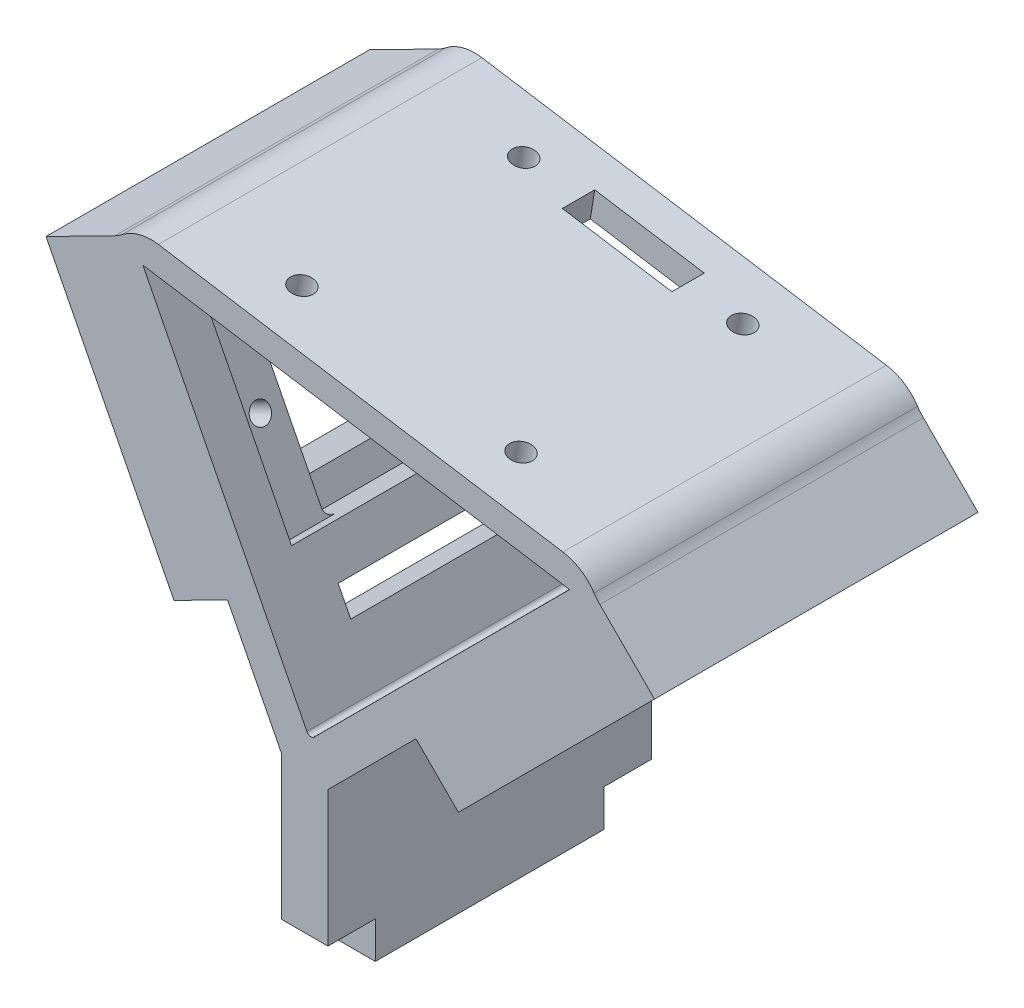
SolidWorks part; units mm, degrees
ref_plane "Front Plane" through (0, 0, 0) normal (0, 0, 1) x (1, 0, 0)
ref_plane "Top Plane" through (0, 0, 0) normal (0, 1, 0) x (1, 0, 0)
ref_plane "Right Plane" through (0, 0, 0) normal (1, 0, 0) x (0, 0, -1)
sketch "Sketch1" plane through (0, 0, 0) normal (0, 0, 1) x (1, 0, 0)
  line L0 (6.55, 4.55) -> (-6.55, 4.55)
  line L1 (4.05, 2.05) -> (-4.05, 2.05)
  line L2 (4.05, 2.05) -> (4.05, -2.05)
  line L3 (4.05, -2.05) -> (2.05, -2.05)
  line L4 (-4.05, 2.05) -> (-4.05, -2.05)
  line L5 (4.05, 2.05) -> (-4.05, -2.05) construction
  line L6 (4.05, -2.05) -> (-4.05, 2.05) construction
  line L7 (-6.55, 4.55) -> (-6.55, -4.55)
  line L8 (6.55, -4.55) -> (2.05, -4.55)
  line L9 (6.55, 4.55) -> (6.55, -4.55)
  line L10 (0, 0) -> (0, -4.55) construction
  line L11 (-2.05, -2.05) -> (-2.05, -4.55)
  line L12 (2.05, -2.05) -> (2.05, -4.55)
  line L13 (-2.05, -4.55) -> (-6.55, -4.55)
  line L14 (6.55, -4.55) -> (-6.55, -4.55) construction
  line L15 (-2.05, -2.05) -> (-4.05, -2.05)
  line L16 (4.05, -2.05) -> (-4.05, -2.05) construction
  line L17 (0, -2.05) -> (0, -4.55) construction
  point P0 (0, 0)
  dimension "D1" = 8.1
  dimension "D2" = 4.1
  dimension "D6" = 4.1
  dimension "D3" = 2.5
  dimension "D4" = 2.05
  dimension "D5" = 2.05
extrude "Boss-Extrude1" add sketch "Sketch1" along normal blind 35
sketch "Sketch2" plane through (0, 0, 35) normal (0, 0, 1) x (1, 0, 0)
  line L0 (0, 4.55) -> (0, 29.55) construction
  line L1 (6.55, 4.55) -> (-6.55, 4.55) construction
  line L2 (2.5, 4.55) -> (2.5, 25.7216)
  line L3 (-2.5, 4.55) -> (-2.5, 26.5511)
  line L4 (-2.5, 4.55) -> (2.5, 4.55)
  line L6 (0, 26.05) -> (31.8198, 57.8698) construction
  line L7 (0, 26.05) -> (-20.4296, 66.1453) construction
  line L8 (2.5, 25.7216) -> (33.234, 56.4556)
  line L9 (0.5323, 29.4107) -> (30.4056, 59.284)
  line L10 (1.4142, 24.6358) -> (33.234, 56.4556) construction
  line L11 (-2.5, 26.5511) -> (-22.2116, 65.2373)
  line L12 (-1.782, 25.142) -> (-22.2116, 65.2373) construction
  line L13 (-1.4142, 27.4642) -> (30.4056, 59.284) construction
  line L14 (0.5323, 29.4107) -> (-18.6476, 67.0533)
  line L15 (2.5, 4.55) -> (2.5, 29.55) construction
  line L17 (-2.5, 4.55) -> (-2.5, 29.55) construction
  line L18 (30.4056, 59.284) -> (33.234, 56.4556)
  line L19 (-22.2116, 65.2373) -> (-18.6476, 67.0533)
  dimension "D1" = 25
  dimension "D4" = 27
  dimension "D5" = 45
  dimension "D6" = 3.5
  dimension "D7" = 45
  dimension "D8" = 45
  dimension "D11" = 2
  dimension "D2" = 2.5
  dimension "D3" = 2.5
  dimension "D9" = 2
  dimension "D10" = 2
  dimension "D12" = 2
extrude "Boss-Extrude2" add sketch "Sketch2" against normal through all
fillet "Fillet1" radius 0.5 1 edges at (0.5323, 29.4107, 17.5)
sketch "Sketch3" plane through (-14.4392, 14.4392, 0) normal (-0.7071, 0.7071, 0) x (0, 0, 1)
  line L0 (0, 63.4201) -> (35, 63.4201) construction
  line L1 (4.5, 60.4201) -> (30.5, 60.4201)
  line L2 (4.5, 60.4201) -> (4.5, 35.4201)
  line L3 (4.5, 35.4201) -> (30.5, 35.4201)
  line L4 (30.5, 60.4201) -> (30.5, 35.4201)
  line L5 (4.5, 60.4201) -> (30.5, 35.4201) construction
  line L6 (4.5, 35.4201) -> (30.5, 60.4201) construction
  line L7 (17.5, 47.9201) -> (17.5, 63.4201) construction
  point P0 (17.5, 47.9201)
  dimension "D1" = 3
  dimension "D2" = 25
  dimension "D3" = 26
extrude "Cut-Extrude1" cut sketch "Sketch3" against normal blind 1.5
sketch "Sketch4" plane through (-13.3786, 13.3786, 0) normal (-0.7071, 0.7071, 0) x (0, 0, 1)
  line L2 (25.5, 35.4201) -> (25.5, 60.4201)
  line L3 (25.5, 35.4201) -> (25.5, 60.4201)
  line L4 (9.5, 60.4201) -> (25.5, 60.4201)
  line L5 (9.5, 60.4201) -> (9.5, 35.4201)
  line L6 (9.5, 60.4201) -> (9.5, 35.4201)
  line L7 (9.5, 35.4201) -> (26.4646, 35.4201)
  line M4 (30.5, 60.4201) -> (4.5, 60.4201)
  line M6 (4.5, 35.4201) -> (30.5, 35.4201)
  dimension "D1" = 5
  dimension "D2" = 5
extrude "Cut-Extrude2" cut sketch "Sketch4" against normal blind 5 contours L6 L3 M4 M6 region at (20.5061, 47.2632, 17.5)
fillet "Fillet3" radius 1 4 edges at (30.2288, 55.2182, 9.5) (30.2288, 55.2182, 25.5) (12.5511, 37.5405, 25.5) (12.5511, 37.5405, 9.5)
sketch "Sketch5" plane through (12.3195, 6.2771, 0) normal (0.891, 0.454, 0) x (0, 0, -1)
  line L0 (-17.5, 68.2107) -> (-17.5, 52.7107) construction
  line L1 (-30.5, 65.2107) -> (-4.5, 65.2107)
  line L2 (-30.5, 65.2107) -> (-30.5, 40.2107)
  line L3 (-30.5, 40.2107) -> (-4.5, 40.2107)
  line L4 (-4.5, 65.2107) -> (-4.5, 40.2107)
  line L5 (-30.5, 65.2107) -> (-4.5, 40.2107) construction
  line L6 (-30.5, 40.2107) -> (-4.5, 65.2107) construction
  line L7 (0, 68.2107) -> (-35, 68.2107) construction
  point P0 (-17.5, 52.7107)
  dimension "D1" = 3
  dimension "D2" = 25
  dimension "D3" = 26
extrude "Cut-Extrude3" cut sketch "Sketch5" against normal blind 1.5
sketch "Sketch6" plane through (10.9829, 5.5961, 0) normal (0.891, 0.454, 0) x (0, 0, -1)
  line L2 (-25.5, 65.2107) -> (-25.5, 40.2107)
  line L3 (-25.5, 65.2107) -> (-25.5, 40.2107)
  line L4 (-9.5, 65.2107) -> (-25.5, 65.2107)
  line L5 (-9.5, 40.2107) -> (-9.5, 65.2107)
  line L6 (-9.5, 40.2107) -> (-9.5, 65.2107)
  line L7 (-25.5, 40.2107) -> (-9.5, 40.2107)
  dimension "D1" = 5
  dimension "D2" = 5
extrude "Cut-Extrude4" cut sketch "Sketch6" against normal blind 5
fillet "Fillet4" radius 1 4 edges at (-8.3861, 40.8566, 9.5) (-19.7359, 63.1318, 9.5) (-19.7359, 63.1318, 25.5) (-8.3861, 40.8566, 25.5)
sketch "Sketch8" plane through (-11.6108, 11.6108, 0) normal (0.7071, -0.7071, 0) x (0, 0, -1)
  line L0 (-17.5, 29.4201) -> (-17.5, 35.4201) construction
  line L1 (-27.5, 30.9201) -> (-7.5, 30.9201)
  line L2 (-27.5, 30.9201) -> (-27.5, 27.9201)
  line L3 (-27.5, 27.9201) -> (-7.5, 27.9201)
  line L4 (-7.5, 30.9201) -> (-7.5, 27.9201)
  line L5 (-27.5, 30.9201) -> (-7.5, 27.9201) construction
  line L6 (-27.5, 27.9201) -> (-7.5, 30.9201) construction
  line L7 (-24.5, 35.4201) -> (-10.5, 35.4201) construction
  point P0 (-17.5, 29.4201)
  dimension "D1" = 3
  dimension "D2" = 6
  dimension "D3" = 20
extrude "Cut-Extrude5" cut sketch "Sketch8" against normal blind 4
sketch "Sketch9" plane through (8.7554, 4.4611, 0) normal (-0.891, -0.454, 0) x (0, 0, 1)
  line L0 (17.5, 40.2107) -> (17.5, 34.2107) construction
  line L2 (10.5, 40.2107) -> (24.5, 40.2107) construction
  line L3 (7.5, 35.7107) -> (27.5, 35.7107)
  line L4 (7.5, 35.7107) -> (7.5, 32.7107)
  line L5 (7.5, 32.7107) -> (27.5, 32.7107)
  line L6 (27.5, 35.7107) -> (27.5, 32.7107)
  line L7 (7.5, 35.7107) -> (27.5, 32.7107) construction
  line L8 (7.5, 32.7107) -> (27.5, 35.7107) construction
  dimension "D1" = 6
  dimension "D2" = 20
  dimension "D3" = 3
extrude "Cut-Extrude6" cut sketch "Sketch9" against normal blind 4
sketch "Sketch10" plane through (-2.5, 0, 0) normal (-1, 0, 0) x (0, 0, 1)
  line L2 (17.5, 4.55) -> (17.5, 19.55) construction
  line L3 (35, 4.55) -> (0, 4.55) construction
  line L4 (7.5, 21.05) -> (27.5, 21.05)
  line L5 (7.5, 21.05) -> (7.5, 18.05)
  line L6 (7.5, 18.05) -> (27.5, 18.05)
  line L7 (27.5, 21.05) -> (27.5, 18.05)
  line L8 (7.5, 21.05) -> (27.5, 18.05) construction
  line L9 (7.5, 18.05) -> (27.5, 21.05) construction
  point P6 (17.5, 19.55)
  dimension "D1" = 20
  dimension "D2" = 3
  dimension "D3" = 15
extrude "Cut-Extrude7" cut sketch "Sketch10" against normal blind 4
sketch "Sketch11" plane through (-13.3786, 13.3786, 0) normal (-0.7071, 0.7071, 0) x (0, 0, 1)
  line L0 (7, 45.4201) -> (7, 57.9201) construction
  line L1 (7, 57.9201) -> (28, 57.9201) construction
  line L2 (28, 57.9201) -> (28, 45.4201) construction
  line L3 (28, 45.4201) -> (7, 45.4201) construction
  line L4 (30.5, 60.4201) -> (4.5, 60.4201) construction
  line L5 (4.5, 60.4201) -> (4.5, 35.4201) construction
  circle A1 centre (28, 57.9201) radius 1.1
  circle A3 centre (7, 57.9201) radius 1.1
  circle A5 centre (28, 45.4201) radius 1.1
  circle A7 centre (7, 45.4201) radius 1.1
  dimension "D3" = 2.2
  dimension "D1" = 21
  dimension "D2" = 12.5
  dimension "D4" = 2.5
  dimension "D5" = 2.5
extrude "Cut-Extrude8" cut sketch "Sketch11" against normal blind 10
sketch "Sketch12" plane through (10.9829, 5.5961, 0) normal (0.891, 0.454, 0) x (0, 0, -1)
  line L0 (-28, 62.7107) -> (-28, 50.2107) construction
  line L2 (-28, 50.2107) -> (-7, 50.2107) construction
  line L5 (-7, 50.2107) -> (-7, 62.7107) construction
  line L6 (-7, 62.7107) -> (-28, 62.7107) construction
  line L7 (-4.5, 65.2107) -> (-30.5, 65.2107) construction
  line L8 (-30.5, 65.2107) -> (-30.5, 40.2107) construction
  circle A1 centre (-7, 62.7107) radius 1.1
  circle A3 centre (-28, 62.7107) radius 1.1
  circle A5 centre (-7, 50.2107) radius 1.1
  circle A7 centre (-28, 50.2107) radius 1.1
  dimension "D5" = 2.2
  dimension "D1" = 12.5
  dimension "D2" = 21
  dimension "D3" = 2.5
  dimension "D4" = 2.5
extrude "Cut-Extrude9" cut sketch "Sketch12" against normal blind 5
sketch "Sketch14" plane through (6.55, 0, 0) normal (1, 0, 0) x (0, 0, -1)
  line L0 (-35, -0.1) -> (0, 0) construction
  line L3 (-35, 1.8508) -> (0, 1.8508)
  line L4 (-35, 1.8508) -> (-35, -1.9508)
  line L5 (-35, -1.9508) -> (0, -1.9508)
  line L6 (0, 1.8508) -> (0, -1.9508)
  line L7 (-35, 1.8508) -> (0, -1.9508) construction
  line L8 (-35, -1.9508) -> (0, 1.8508) construction
  point P5 (-17.5, -0.05)
extrude "Boss-Extrude3" add sketch "Sketch14" along normal blind 3.5 and the other way blind 1
sketch "Sketch15" plane through (0, 1.8508, 0) normal (0, 1, 0) x (1, 0, 0)
  line L6 (6.55, -35) -> (6.55, 0) construction
  line L7 (6.55, -33) -> (6.55, -2)
  line L9 (8.05, -33) -> (6.55, -33)
  line L10 (6.55, -2) -> (8.05, -2)
  line L11 (8.05, -2) -> (8.05, -33)
  line L12 (8.05, -33) -> (6.55, -33)
  line L13 (6.55, -2) -> (8.05, -2)
  line L14 (8.05, -2) -> (8.05, -33)
  dimension "D1" = 2
extrude "Cut-Extrude10" cut sketch "Sketch15" against normal blind 5
sketch "Sketch16" plane through (0, 4.55, 0) normal (0, 1, 0) x (1, 0, 0)
  line L1 (-30.4197, 7.2021) -> (26.8386, 7.2021)
  line L2 (-30.4197, 7.2021) -> (-30.4197, -38.2329)
  line L3 (-30.4197, -38.2329) -> (26.8386, -38.2329)
  line L4 (26.8386, 7.2021) -> (26.8386, -38.2329)
  line L5 (-30.4197, 7.2021) -> (26.8386, -38.2329) construction
  line L6 (-30.4197, -38.2329) -> (26.8386, 7.2021) construction
  point P0 (-1.7905, -15.5154)
extrude "Cut-Extrude11" [suppressed] cut sketch "Sketch16" against normal blind 10 and the other way blind 1
sketch "Sketch18" plane through (-11.6108, 11.6108, 0) normal (0.7071, -0.7071, 0) x (0, 0, -1)
  line L0 (-35, 19.9557) -> (-35, 63.4201) construction
  line L1 (0, 19.9557) -> (0, 63.4201) construction
  line L2 (0, 63.4201) -> (-35, 63.4201) construction
  line L3 (-35, 33.4201) -> (-35, 63.4201)
  line L4 (0, 33.4201) -> (0, 63.4201)
  line L5 (0, 63.4201) -> (-35, 63.4201)
  line L6 (-25.5, 59.4201) -> (-25.5, 36.4201) construction
  line L7 (-9.5, 36.4201) -> (-9.5, 59.4201) construction
  line L9 (-25.5, 58.9201) -> (-25.5, 38.9201)
  line L10 (-9.5, 38.9201) -> (-9.5, 58.9201)
  line L11 (-35, 33.4201) -> (0, 33.4201)
  line L12 (-25.5, 58.9201) -> (-9.5, 58.9201)
  line L13 (-25.5, 38.9201) -> (-9.5, 38.9201)
  line L14 (-24.5, 35.4201) -> (-10.5, 35.4201) construction
  circle A4 centre (-7, 57.9201) radius 1.1 construction
  circle A5 centre (-7, 45.4201) radius 1.1 construction
  circle A6 centre (-28, 45.4201) radius 1.1 construction
  circle A7 centre (-28, 57.9201) radius 1.1 construction
  circle A8 centre (-7, 57.9201) radius 1.1
  circle A9 centre (-7, 45.4201) radius 1.1
  circle A10 centre (-28, 45.4201) radius 1.1
  circle A11 centre (-28, 57.9201) radius 1.1
  dimension "D1" = 2
  dimension "D2" = 4.5
  dimension "D3" = 3.5
extrude "Boss-Extrude4" add sketch "Sketch18" along normal blind 6.5
sketch "Sketch19" plane through (8.7554, 4.4611, 0) normal (-0.891, -0.454, 0) x (0, 0, 1)
  line L0 (25.5, 41.2107) -> (25.5, 64.2107) construction
  line L1 (9.5, 64.2107) -> (9.5, 41.2107) construction
  line L2 (25.5, 43.2107) -> (25.5, 60.7107)
  line L3 (9.5, 60.7107) -> (9.5, 43.2107)
  line L4 (35, 68.2107) -> (0, 68.2107)
  line L5 (0, 68.2107) -> (0, 24.7922)
  line L6 (0, 24.7922) -> (35, 24.7922)
  line L7 (35, 24.7922) -> (35, 68.2107)
  line L8 (35, 68.2107) -> (0, 68.2107)
  line L9 (0, 68.2107) -> (0, 37.7107)
  line L11 (35, 37.7107) -> (35, 68.2107)
  line L12 (9.5, 60.7107) -> (25.5, 60.7107)
  line L13 (9.5, 43.2107) -> (25.5, 43.2107)
  line L14 (24.5, 65.2107) -> (10.5, 65.2107) construction
  line L15 (10.5, 40.2107) -> (24.5, 40.2107) construction
  line L16 (0, 37.7107) -> (35, 37.7107)
  circle A0 centre (28, 62.7107) radius 1.1 construction
  circle A1 centre (28, 50.2107) radius 1.1 construction
  circle A6 centre (7, 50.2107) radius 1.1 construction
  circle A7 centre (7, 62.7107) radius 1.1 construction
  circle A8 centre (28, 50.2107) radius 1.1
  circle A9 centre (7, 50.2107) radius 1.1
  circle A10 centre (7, 62.7107) radius 1.1
  circle A11 centre (28, 62.7107) radius 1.1
  dimension "D2" = 4.5
  dimension "D3" = 3
  dimension "D4" = 2.5
  dimension "D1" = 0
extrude "Boss-Extrude5" add sketch "Sketch19" along normal blind 6.5
sketch "Sketch20" plane through (0, 4.55, 0) normal (0, 1, 0) x (1, 0, 0)
  line L1 (-46.7008, 10.2311) -> (46.7008, 10.2311)
  line L2 (-46.7008, 10.2311) -> (-46.7008, -43.0242)
  line L3 (-46.7008, -43.0242) -> (46.7008, -43.0242)
  line L4 (46.7008, 10.2311) -> (46.7008, -43.0242)
  line L5 (-46.7008, 10.2311) -> (46.7008, -43.0242) construction
  line L6 (-46.7008, -43.0242) -> (46.7008, 10.2311) construction
  point P0 (0, -16.3965)
extrude "Cut-Extrude12" cut sketch "Sketch20" against normal blind 10 and the other way blind 2.5
sketch "Sketch21" plane through (0, 0, 35) normal (0, 0, 1) x (1, 0, 0)
  line L0 (2.5, 7.05) -> (2.5, 25.7216) construction
  line L1 (-2.5, 7.05) -> (2.5, 7.05)
  line L2 (-2.5, 7.05) -> (-2.5, 11.05)
  line L3 (-2.5, 11.05) -> (2.5, 11.05)
  line L4 (2.5, 7.05) -> (2.5, 11.05)
  dimension "D1" = 4
extrude "Cut-Extrude13" cut sketch "Sketch21" against normal blind 5.125
ref_plane "Plane1" through (0, 0, 17.5) normal (0, 0, -1) x (-1, 0, 0)
mirror "Mirror1" about plane through (0, 0, 17.5) normal (0, 0, -1) of "Cut-Extrude13"
fillet "Fillet9" radius 2 4 edges at (-21.7024, 57.0793, 25.5) (-13.7576, 41.4867, 9.5) (-13.7576, 41.4867, 25.5) (-21.7024, 57.0793, 9.5)
fillet "Fillet10" radius 2 4 edges at (32.3501, 50.9755, 9.5) (32.3501, 50.9755, 25.5) (18.208, 36.8334, 25.5) (18.208, 36.8334, 9.5)
sketch "Sketch22" plane through (0, 0, 35) normal (0, 0, 1) x (1, 0, 0)
  line L0 (-18.0758, 64.935) -> (29.4542, 57.407)
  line L1 (29.4542, 57.407) -> (32.8149, 56.8747)
  line L3 (32.8149, 56.8747) -> (30.4056, 59.284)
  line L4 (30.4056, 59.284) -> (-18.6476, 67.0533)
  line L5 (-18.6476, 67.0533) -> (-20.4498, 65.9701)
  line L7 (-20.4498, 65.9701) -> (-18.0758, 64.935)
  line L8 (37.8302, 51.8594) -> (30.4056, 59.284) construction
  point P4 (0, 0)
  point P6 (0, 0)
  point P13 (0, 0)
  point P14 (0, 0)
  point P15 (0, 0)
  point P16 (0, 0)
  point P17 (0, 0)
  point P20 (0, 0)
extrude "Boss-Extrude6" add sketch "Sketch22" against normal through all
sketch "Sketch23" plane through (9.904, 62.5312, 0) normal (0.1564, 0.9877, 0) x (0.9877, -0.1564, 0)
  line L4 (-28.9074, -35) -> (20.7572, -35)
  line L5 (-28.9074, 0) -> (-28.9074, -35)
  line L6 (20.7572, 0) -> (-28.9074, 0)
  line L8 (-28.9074, -35) -> (20.7572, -35)
  line L10 (20.7572, 0) -> (-28.9074, 0)
  line L12 (-28.9074, 0) -> (-28.9074, -35)
  line L14 (20.7572, -35) -> (20.7572, 0)
  line L16 (20.7572, -35) -> (20.7572, 0)
  dimension "D1" = 0
extrude "Boss-Extrude7" add sketch "Sketch23" along normal blind 1
sketch "Sketch24" plane through (10.0604, 63.5188, 0) normal (0.1564, 0.9877, 0) x (0.9877, -0.1564, 0)
  line L0 (-4.0751, -35) -> (-4.0751, 0) construction
  line L1 (-28.9074, -35) -> (20.7572, -35) construction
  line L2 (20.7572, 0) -> (-28.9074, 0) construction
  line L3 (-16.0751, -5.5) -> (-16.0751, -29.5) construction
  line L4 (-18.0751, -3.5) -> (9.9249, -3.5) construction
  line L5 (-18.0751, -3.5) -> (-18.0751, -31.5) construction
  line L6 (-18.0751, -31.5) -> (9.9249, -31.5) construction
  line L7 (9.9249, -3.5) -> (9.9249, -31.5) construction
  line L8 (-18.0751, -3.5) -> (9.9249, -31.5) construction
  line L9 (-18.0751, -31.5) -> (9.9249, -3.5) construction
  line L10 (-16.0751, -29.5) -> (7.9249, -29.5) construction
  line L11 (7.9249, -29.5) -> (7.9249, -5.5) construction
  line L12 (7.9249, -5.5) -> (-16.0751, -5.5) construction
  line L14 (-10.0751, -3.75) -> (1.9249, -3.75)
  line L15 (-10.0751, -3.75) -> (-10.0751, -7.25)
  line L16 (-10.0751, -7.25) -> (1.9249, -7.25)
  line L17 (1.9249, -3.75) -> (1.9249, -7.25)
  line L18 (-10.0751, -3.75) -> (1.9249, -7.25) construction
  line L19 (-10.0751, -7.25) -> (1.9249, -3.75) construction
  circle A0 centre (-16.0751, -5.5) radius 1.25
  circle A1 centre (7.9249, -5.5) radius 1.25
  circle A2 centre (7.9249, -29.5) radius 1.25
  circle A3 centre (-16.0751, -29.5) radius 1.25
  point P6 (-4.0751, -17.5)
  point P19 (-4.0751, -5.5)
  dimension "D7" = 2.5
  dimension "D1" = 28
  dimension "D2" = 28
  dimension "D3" = 24
  dimension "D4" = 24
  dimension "D5" = 12
  dimension "D6" = 3.5
extrude "Cut-Extrude14" cut sketch "Sketch24" against normal blind 5
fillet "Fillet13" radius 5 2 edges at (-18.6476, 67.0533, 17.5) (30.4056, 59.284, 17.5)
fillet "Fillet14" radius 5 2 edges at (-18.4911, 68.041, 17.5) (30.562, 60.2717, 17.5)
